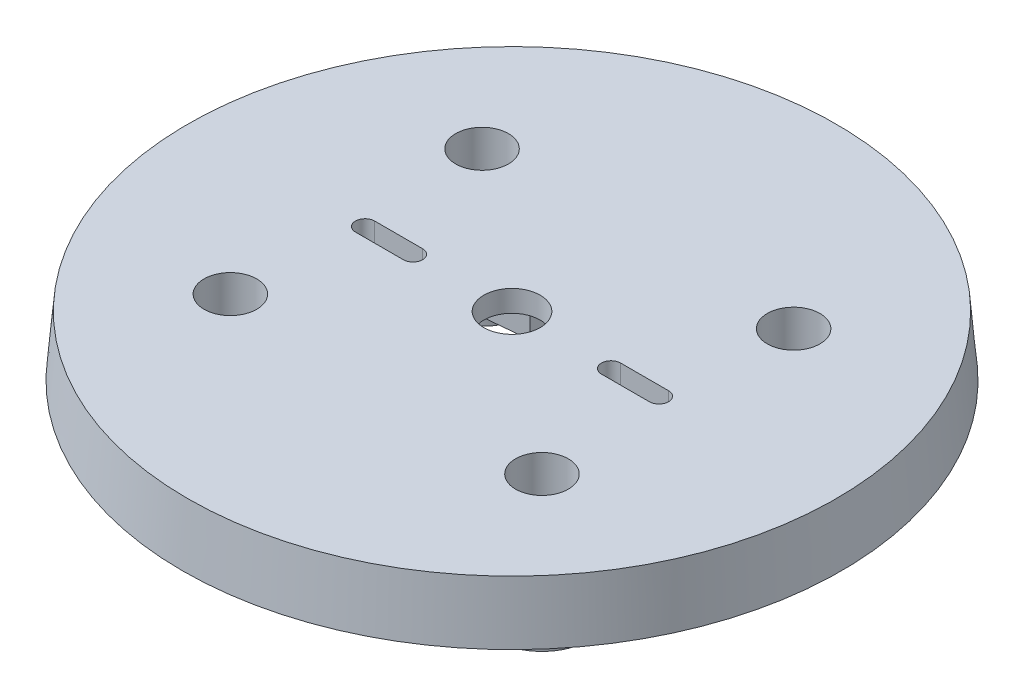
SolidWorks part; units mm, degrees
ref_plane "Ön Düzlem" through (0, 0, 0) normal (0, 0, 1) x (1, 0, 0)
ref_plane "Üst Düzlem" through (0, 0, 0) normal (0, 1, 0) x (1, 0, 0)
ref_plane "Sağ Düzlem" through (0, 0, 0) normal (1, 0, 0) x (0, 0, -1)
sketch "Çizim2" plane through (0, 0, 0) normal (0, 1, 0) x (1, 0, 0)
  circle A0 centre (0, 0) radius 27.5
  dimension "D1" = 55
extrude "Yükseklik-Ekstrüzyon1" add sketch "Çizim2" along normal blind 5 draft 5
sketch "Çizim3" plane through (0, 0, 0) normal (0, 0, 1) x (1, 0, 0)
  line L0 (17.3267, 5) -> (9.6216, 26.1695)
  line L1 (3.213, 29.1579) -> (-17.3834, 21.6614)
  line L2 (-20.6733, 16.9629) -> (-20.6733, 5)
  line L3 (27.0626, 5) -> (-27.0626, 5) construction
  line L4 (4.2391, 26.3388) -> (8.7537, 13.9349)
  line L5 (4.2391, 26.3388) -> (-17.5618, 18.4039)
  line L6 (8.7537, 13.9349) -> (-13.0471, 6)
  line L7 (-17.5618, 18.4039) -> (-13.0471, 6)
  line L8 (-17.4188, 11.4324) -> (8.6107, 20.9064) construction
  line L9 (17.3267, 5) -> (-20.6733, 5)
  line L10 (-2.1467, 9.9674) -> (-4.404, 16.1694) construction
  line L11 (8.6107, 20.9064) -> (6.4964, 20.1368) construction
  line L12 (8.8843, 20.1546) -> (6.77, 19.3851)
  line L13 (8.3371, 21.6581) -> (6.2228, 20.8886)
  line L14 (8.6242, 18.6765) -> (5.8051, 17.6505)
  line L15 (8.6242, 18.6765) -> (7.1877, 22.6232)
  line L16 (5.8051, 17.6505) -> (4.3686, 21.5972)
  line L17 (7.1877, 22.6232) -> (4.3686, 21.5972)
  line L18 (8.6242, 18.6765) -> (4.3686, 21.5972) construction
  line L19 (5.8051, 17.6505) -> (7.1877, 22.6232) construction
  arc A0 (-17.3834, 21.6614) -> (-20.6733, 16.9629) centre (-15.6733, 16.9629) ccw
  arc A1 (9.6216, 26.1695) -> (3.213, 29.1579) centre (4.9231, 24.4594) ccw
  circle A2 centre (8.6107, 20.9064) radius 0.8 construction
  circle A3 centre (-17.4188, 11.4324) radius 0.8
  arc A4 (8.8843, 20.1546) -> (8.3371, 21.6581) centre (8.6107, 20.9064) ccw
  arc A5 (6.2228, 20.8886) -> (6.77, 19.3851) centre (6.4964, 20.1368) ccw
  point P2 (6.4964, 20.1368)
  point P10 (7.5536, 20.5216)
  point P28 (6.4964, 20.1368)
  dimension "D4" = 5
  dimension "D9" = 1.6
  dimension "D10" = 27.7
  dimension "D1" = 13.2
  dimension "D2" = 70
  dimension "D3" = 23.2
  dimension "D5" = 1
  dimension "D6" = 38
  dimension "D7" = 3
  dimension "D8" = 5
  dimension "D11" = 1.6
  dimension "D13" = 3
  dimension "D14" = 4.2
extrude "Yükseklik-Ekstrüzyon2" [suppressed] add sketch "Çizim3" against normal blind 10 and the other way blind 2 contours L5 L7 L6 L4 | A3 | A2 | A5 L4 L17 L16 L14 | L14 L15 L12 L4 | L15 L17 L4 L13 | L9 L2 A0 L1 A1 L0 | L13 A5 L12 A4
sketch "Çizim4" plane through (0, 0, 0) normal (0, -1, 0) x (1, 0, 0)
  line L0 (27.5, 0) -> (-27.5, 0) construction
  line L1 (15.9279, 2.3882) -> (2.2, 3.692)
  line L2 (2.2, 3.692) -> (2.2, 7.45)
  line L3 (-2.2, 7.45) -> (-2.2, 3.692)
  line L4 (15.909, 2.1891) -> (2, 3.5101) construction
  line L5 (2, 3.5101) -> (2, 7.45) construction
  line L6 (-2, 7.45) -> (-2, 3.5101) construction
  line L7 (-2, 3.5101) -> (-15.909, 2.1891) construction
  line L8 (-15.909, -2.1891) -> (-2, -3.5101) construction
  line L9 (-2, -3.5101) -> (-2, -7.45) construction
  line L10 (2, -7.45) -> (2, -3.5101) construction
  line L11 (2, -3.5101) -> (15.909, -2.1891) construction
  line L12 (-2.2, 3.692) -> (-15.9279, 2.3882)
  line L13 (-15.9279, -2.3882) -> (-2.2, -3.692)
  line L14 (-2.2, -3.692) -> (-2.2, -7.45)
  line L15 (2.2, -7.45) -> (2.2, -3.692)
  line L16 (2.2, -3.692) -> (15.9279, -2.3882)
  line L17 (0, 11) -> (0, 0) construction
  circle A0 centre (0, 0) radius 27.5 construction
  arc A1 (2, 7.45) -> (-2, 7.45) centre (0, 7.45) ccw construction
  arc A2 (-15.909, 2.1891) -> (-15.909, -2.1891) centre (-15.7011, 0) ccw construction
  arc A3 (-2, -7.45) -> (2, -7.45) centre (0, -7.45) ccw construction
  arc A4 (15.909, -2.1891) -> (15.909, 2.1891) centre (15.7011, 0) ccw construction
  circle A5 centre (0, 0) radius 2.35
  circle A6 centre (0, 0) radius 3.625
  circle A7 centre (-8.3188, 0) radius 0.7 construction
  circle A8 centre (-12.9188, 0) radius 0.7 construction
  circle A9 centre (0, 7.45) radius 0.7 construction
  circle A10 centre (0, -7.45) radius 0.7 construction
  circle A11 centre (8.3188, 0) radius 0.7 construction
  circle A12 centre (12.9188, 0) radius 0.7 construction
  arc A13 (2.2, 7.45) -> (-2.2, 7.45) centre (0, 7.45) ccw
  arc A14 (-15.9279, 2.3882) -> (-15.9279, -2.3882) centre (-15.7011, 0) ccw
  arc A15 (-2.2, -7.45) -> (2.2, -7.45) centre (0, -7.45) ccw
  arc A16 (15.9279, -2.3882) -> (15.9279, 2.3882) centre (15.7011, 0) ccw
  dimension "D1" = 11
extrude "Kes-Ekstrüzyon1" cut sketch "Çizim4" against normal blind 2.4 contours L16 A16 L1 L2 A13 L3 L12 A14 L13 L14 A15 L15 A6 region at (17.6898, 0, 0)
extrude "Kes-Ekstrüzyon2" cut sketch "Çizim4<3>" against normal blind 14 contours A5 region at (0, 0, 0)
sketch "Çizim4<3>" plane through (0, 0, 0) normal (0, -1, 0) x (1, 0, 0) same geometry as "Çizim4"
sketch "Çizim8" plane through (0, 0, 0) normal (0, -1, 0) x (1, 0, 0)
  line L0 (2.2, -3.692) -> (15.9279, -2.3882) construction
  line L1 (-5, 3.426) -> (5, 3.426) construction
  line L2 (-5, 3.426) -> (-5, -3.426)
  line L3 (-5, -3.426) -> (5, -3.426) construction
  line L4 (5, 3.426) -> (5, -3.426)
  line L5 (-5, 3.426) -> (5, -3.426) construction
  line L6 (-5, -3.426) -> (5, 3.426) construction
  line L7 (15.9279, 2.3882) -> (2.2, 3.692) construction
  line L9 (2.2, -3.692) -> (15.9279, -2.3882) construction
  line L13 (-2.2, 3.692) -> (-15.9279, 2.3882) construction
  line L14 (-15.9279, -2.3882) -> (-2.2, -3.692) construction
  line L15 (2.2, -3.692) -> (5, -3.426)
  line L16 (5, 3.426) -> (2.2, 3.692)
  line L17 (-2.2, 3.692) -> (-5, 3.426)
  line L18 (-5, -3.426) -> (-2.2, -3.692)
  spline S0 degree 1 poles (2.2, 3.692) (-2.2, 3.692) knots 0 0 1 1
  spline S1 degree 1 poles (2.2, -3.692) (-2.2, -3.692) knots 0 0 1 1
  point P0 (0, 0)
  dimension "D1" = 10
extrude "Kes-Ekstrüzyon3" cut sketch "Çizim8" against normal blind 3.2
sketch "Çizim9" plane through (0, 2.4, 0) normal (0, -1, 0) x (1, 0, 0)
  line L0 (12.2628, 0) -> (8.2628, 0) construction
  line L1 (12.2628, -0.8) -> (8.2628, -0.8)
  line L2 (12.2628, 0.8) -> (8.2628, 0.8)
  line L3 (0, 2.35) -> (0, -2.35) construction
  line L4 (-12.2628, 0) -> (-8.2628, 0) construction
  line L5 (-12.2628, -0.8) -> (-8.2628, -0.8)
  line L6 (-12.2628, 0.8) -> (-8.2628, 0.8)
  arc A0 (12.2628, -0.8) -> (12.2628, 0.8) centre (12.2628, 0) ccw
  arc A1 (8.2628, 0.8) -> (8.2628, -0.8) centre (8.2628, 0) ccw
  circle A2 centre (0, 0) radius 2.35 construction
  arc A3 (-12.2628, -0.8) -> (-12.2628, 0.8) centre (-12.2628, 0) cw
  arc A4 (-8.2628, 0.8) -> (-8.2628, -0.8) centre (-8.2628, 0) cw
  point P2 (10.2628, 0)
  point P15 (-10.2628, 0)
  dimension "D1" = 4
  dimension "D2" = 1.6
extrude "Kes-Ekstrüzyon4" cut sketch "Çizim9" against normal blind 3.5
sketch "Çizim11" plane through (0, 5, 0) normal (0, 1, 0) x (1, 0, 0)
  line L0 (0, 0) -> (0, -4.7462) construction
  line L1 (2.35, 0) -> (2.35, -4.7462)
  line L2 (-2.35, 0) -> (-2.35, -4.7462)
  arc A0 (2.35, 0) -> (-2.35, 0) centre (0, 0) ccw
  arc A1 (-2.35, -4.7462) -> (2.35, -4.7462) centre (0, -4.7462) ccw
  circle A2 centre (0, 0) radius 2.35 construction
  point P2 (0, -2.3731)
extrude "Kes-Ekstrüzyon5" [suppressed] cut sketch "Çizim11" along normal up to next
fillet "Radyus1" [suppressed] radius 4
chamfer "Pah1" [suppressed] distance 5 angle 35
chamfer "Pah2" [suppressed] distance 0.5
sketch "Sketch1" plane through (0, 0, 0) normal (0, -1, 0) x (1, 0, 0)
  line L1 (13, -10.5) -> (-13, -10.5) construction
  line L2 (13, -10.5) -> (13, 10.5) construction
  line L3 (13, 10.5) -> (-13, 10.5) construction
  line L4 (-13, -10.5) -> (-13, 10.5) construction
  line L5 (13, -10.5) -> (-13, 10.5) construction
  line L6 (13, 10.5) -> (-13, -10.5) construction
  circle A0 centre (-13, 10.5) radius 4
  circle A1 centre (13, 10.5) radius 4
  circle A2 centre (13, -10.5) radius 4
  circle A3 centre (-13, -10.5) radius 4
  point P0 (0, 0)
  dimension "D1" = 8
  dimension "D2" = 26
  dimension "D3" = 21
extrude "Boss-Extrude1" add sketch "Sketch1" along normal blind 5
sketch "Sketch3" plane through (0, 5, 0) normal (0, 1, 0) x (1, 0, 0)
  circle A0 centre (13, 10.5) radius 2.2
  circle A1 centre (-13, 10.5) radius 2.2
  circle A2 centre (-13, -10.5) radius 2.2
  circle A3 centre (13, -10.5) radius 2.2
  dimension "D1" = 4.4
extrude "Cut-Extrude1" cut sketch "Sketch3" against normal blind 5.2
chamfer "Chamfer1" distance 2.5 angle 45 4 edges at (-13, 0, -6.5) (13, 0, -6.5) (13, 0, 14.5) (-13, 0, 14.5)
